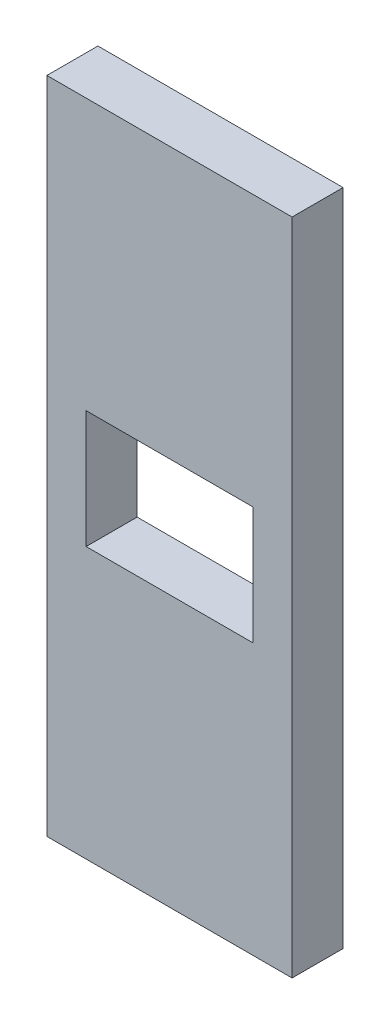
SolidWorks part; units mm, degrees
ref_plane "Front Plane" through (0, 0, 0) normal (0, 0, 1) x (1, 0, 0)
ref_plane "Top Plane" through (0, 0, 0) normal (0, 1, 0) x (1, 0, 0)
ref_plane "Right Plane" through (0, 0, 0) normal (1, 0, 0) x (0, 0, -1)
sketch "Sketch1" plane through (0, 0, 0) normal (0, 0, 1) x (1, 0, 0)
  line L0 (0, 67.2) -> (0, 44.8)
  line L1 (0, 67.2) -> (25, 67.2)
  line L2 (0, 44.8) -> (0, 39.6)
  line L3 (25, 0) -> (0, 0)
  line L4 (4, 39.6) -> (21, 39.6)
  line L5 (4, 27.6) -> (21, 27.6)
  line L6 (4, 39.6) -> (4, 27.6)
  line L7 (21, 39.6) -> (21, 27.6)
  line L8 (0, 44.8) -> (25, 44.8) construction
  line L9 (0, 39.6) -> (25, 39.6) construction
  line L10 (0, 39.6) -> (0, 27.6)
  line L11 (0, 27.6) -> (0, 22.4)
  line L12 (25, 44.8) -> (25, 39.6)
  line L13 (25, 67.2) -> (25, 44.8)
  line L14 (0, 22.4) -> (0, 0)
  line L15 (25, 39.6) -> (25, 27.6)
  line L16 (25, 27.6) -> (25, 22.4)
  line L17 (25, 22.4) -> (25, 0)
  line L18 (0, 27.6) -> (25, 27.6) construction
  line L19 (25, 22.4) -> (0, 22.4) construction
  line L20 (12.5, -0.0005) -> (12.5, 4.0956) construction
  point P18 (12.5, 27.6)
  point P20 (12.5, 39.6)
  point P21 (12.5, 67.2)
  dimension "D1" = 22.4
  dimension "D2" = 12
  dimension "D3" = 5.2
  dimension "D4" = 25
  dimension "D5" = 12
  dimension "D6" = 17
extrude "Boss-Extrude1" add sketch "Sketch1" along normal blind 5.2
